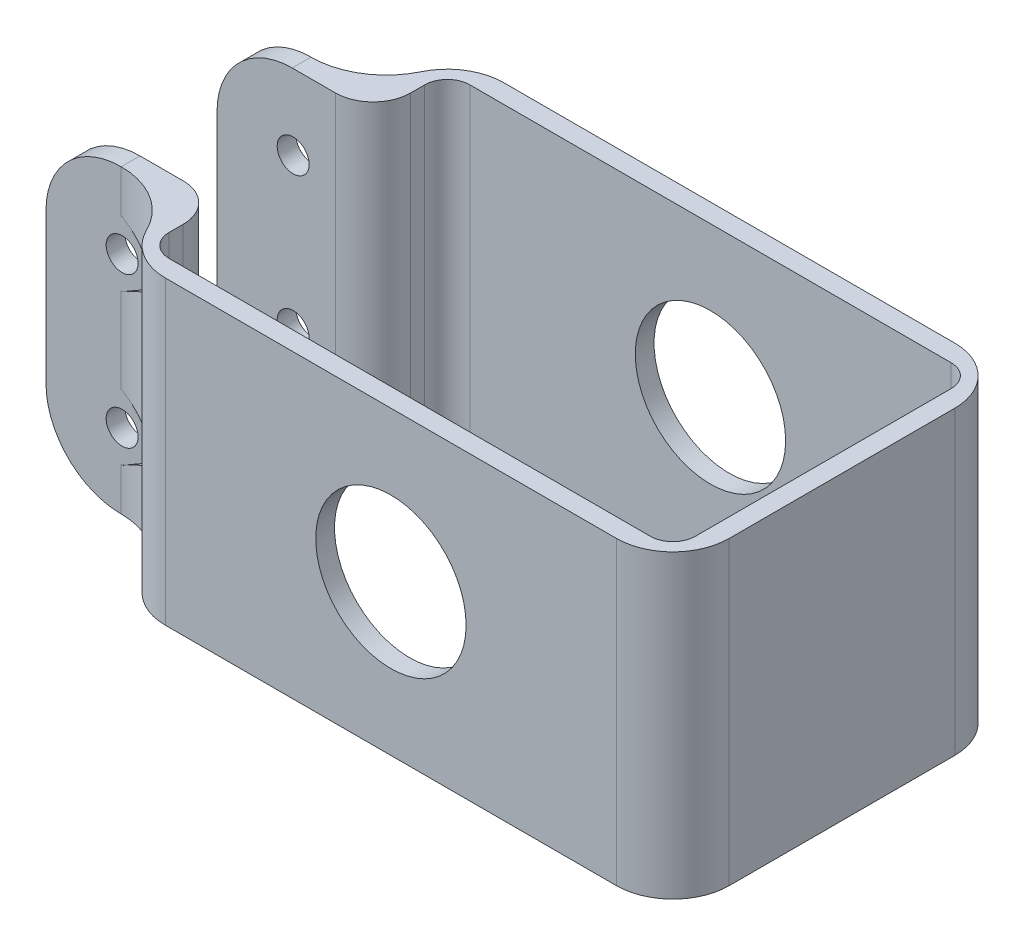
SolidWorks part; units mm, degrees
ref_plane "Front Plane" through (0, 0, 0) normal (0, 0, 1) x (1, 0, 0)
ref_plane "Top Plane" through (0, 0, 0) normal (0, 1, 0) x (1, 0, 0)
ref_plane "Right Plane" through (0, 0, 0) normal (1, 0, 0) x (0, 0, -1)
sketch "Sketch1" plane through (0, 0, 0) normal (0, 1, 0) x (1, 0, 0)
  line L0 (35, -23) -> (-35, -23) construction
  line L1 (35, -8) -> (35, -38) construction
  line L2 (-35, -38) -> (-35, -8) construction
  line L3 (-35, -23) -> (-53.25, -23) construction
  line L5 (-35, -33.125) -> (-53.25, -33.125)
  line L6 (-35, -33.125) -> (-35, -12.875)
  line L7 (-35, -12.875) -> (-53.25, -12.875)
  line L8 (-53.25, -33.125) -> (-53.25, -12.875)
  line L9 (-35, -33.125) -> (-53.25, -12.875) construction
  line L10 (-35, -12.875) -> (-53.25, -33.125) construction
  line L11 (-55.75, -10.375) -> (-35, -10.375)
  line L12 (-55.75, -10.375) -> (-55.75, -35.625)
  line L13 (-55.75, -35.625) -> (-35, -35.625)
  line L14 (-35, -10.375) -> (-35, -35.625)
  line L34 (-35, -10.375) -> (-35, -6)
  line L35 (-32, -3) -> (32, -3)
  line L36 (35, -6) -> (35, -40)
  line L37 (32, -43) -> (-32, -43)
  line L38 (30, -0.5) -> (-30, -0.5)
  line L39 (37.5, -38) -> (37.5, -8)
  line L40 (-30, -45.5) -> (30, -45.5)
  line L41 (-37.5, -8) -> (-37.5, -38)
  line L42 (30, -0.5) -> (-30, -0.5)
  line L43 (37.5, -38) -> (37.5, -8)
  line L44 (-30, -45.5) -> (30, -45.5)
  line L45 (-37.5, -8) -> (-37.5, -38)
  line L46 (-35, -40) -> (-35, -3)
  line L47 (-30, -3) -> (30, -3) construction
  line L48 (30, -43) -> (-30, -43) construction
  line L49 (-53.25, -12.875) -> (-55.75, -12.875)
  line L50 (-53.25, -33.125) -> (-55.75, -33.125)
  arc A22 (-35, -40) -> (-32, -43) centre (-32, -40) ccw
  arc A23 (32, -43) -> (35, -40) centre (32, -40) ccw
  arc A24 (35, -6) -> (32, -3) centre (32, -6) ccw
  arc A25 (-35, -6) -> (-32, -3) centre (-32, -6) cw
  arc A26 (37.5, -8) -> (30, -0.5) centre (30, -8) ccw
  arc A27 (30, -45.5) -> (37.5, -38) centre (30, -38) ccw
  arc A28 (-37.5, -38) -> (-30, -45.5) centre (-30, -38) ccw
  arc A29 (-30, -0.5) -> (-37.5, -8) centre (-30, -8) ccw
  arc A30 (37.5, -8) -> (30, -0.5) centre (30, -8) ccw
  arc A31 (30, -45.5) -> (37.5, -38) centre (30, -38) ccw
  arc A32 (-37.5, -38) -> (-30, -45.5) centre (-30, -38) ccw
  arc A33 (-30, -0.5) -> (-37.5, -8) centre (-30, -8) ccw
  point P6 (-44.125, -23)
  dimension "D7" = 3
  dimension "D1" = 20.25
  dimension "D2" = 18.25
  dimension "D3" = 2.5
  dimension "D4" = 2.5
  dimension "D5" = 2.5
  dimension "D6" = 2.5
extrude "Boss-Extrude1" add sketch "Sketch1" along normal blind 20 and the other way blind 20 contours L5 L50 L12 L13 L45 | L5 L45 L13 L14 | L42 A33 L45 L11 L34 A25 L35 A24 L36 A23 L37 A22 L46 L13 A32 L44 A31 L43 A30 | L11 L45 L7 L14 | L49 L7 L45 L11 L12 region at (-36.25, 0, 34.375) region at (-46.625, 0, 34.375) region at (-36.25, 0, 11.625) region at (-35.8746, 0, 37.8125) region at (-46.625, 0, 11.625)
fillet "Fillet1" radius 10 2 edges at (-37.5, 0, 10.375) (-37.5, 0, 35.625)
sketch "Sketch2" plane through (0, 0, 0) normal (0, 0, 1) x (1, 0, 0)
  line L0 (-45.625, 20) -> (-45.625, -20) construction
  line L1 (-55.75, 20) -> (-45.7515, 20) construction
  line L2 (-55.75, -20) -> (-45.7515, -20) construction
  line L3 (-55.75, -20) -> (-55.75, 20) construction
  circle A0 centre (-45.625, 10) radius 2.125
  circle A1 centre (-45.625, -10) radius 2.125
  circle A2 centre (-45.625, 10) radius 4.25
  circle A3 centre (-45.625, -10) radius 4.25
  dimension "D1" = 4.25
  dimension "D5" = 8.5
  dimension "D2" = 10.125
  dimension "D3" = 10
  dimension "D4" = 10
extrude "Cut-Extrude1" cut sketch "Sketch2" against normal through all both and the other way through all contours L0 A1 | A1 L0 | A0 L0 | L0 A0 region at (-44.7231, 10, 0) region at (-46.5269, 10, 0) region at (-44.7231, -10, 0) region at (-46.5269, -10, 0)
extrude "Cut-Extrude2" cut sketch "Sketch2<4>" along normal up to surface (10.375 mm away) and the other way through all contours A2 L0 A0 | A3 L0 A1 region at (-42.687, 12.938, 0) region at (-42.687, -7.062, 0) up to face at (-48.7507, 0, 10.375)
sketch "Sketch2<4>" plane through (0, 0, 0) normal (0, 0, 1) x (1, 0, 0) same geometry as "Sketch2"
ref_plane "Plane1" through (0, 0, 23) normal (0, 0, -1) x (-1, 0, 0)
fillet "Fillet2" radius 10 4 edges at (-55.75, -20, 11.625) (-55.75, -20, 34.375) (-55.75, 20, 11.625) (-55.75, 20, 34.375)
fillet "Fillet3" radius 5 2 edges at (-35, 0, 12.875) (-35, 0, 33.125)
sketch "Sketch3" plane through (0, 0, 35.625) normal (0, 0, 1) x (1, 0, 0)
  line L1 (-45.625, 14.3301) -> (-49.375, 12.1651)
  line L2 (-49.375, 12.1651) -> (-49.375, 7.8349)
  line L3 (-49.375, 7.8349) -> (-45.625, 5.6699)
  line L4 (-45.625, 5.6699) -> (-41.875, 7.8349)
  line L5 (-41.875, 7.8349) -> (-41.875, 12.1651)
  line L6 (-41.875, 12.1651) -> (-45.625, 14.3301)
  line L7 (-45.625, -5.6699) -> (-49.375, -7.8349)
  line L8 (-49.375, -7.8349) -> (-49.375, -12.1651)
  line L9 (-49.375, -12.1651) -> (-45.625, -14.3301)
  line L10 (-45.625, -14.3301) -> (-41.875, -12.1651)
  line L11 (-41.875, -12.1651) -> (-41.875, -7.8349)
  line L12 (-41.875, -7.8349) -> (-45.625, -5.6699)
  circle A0 centre (-45.625, 10) radius 3.75 construction
  circle A1 centre (-45.625, -10) radius 3.75 construction
  dimension "D1" = 7.5
extrude "Cut-Extrude3" cut sketch "Sketch3" along normal blind 20
sketch "Sketch4" plane through (0, 0, 45.5) normal (0, 0, 1) x (1, 0, 0)
  circle A0 centre (0, 0) radius 10
  dimension "D1" = 20
extrude "Cut-Extrude4" cut sketch "Sketch4" against normal through all both and the other way through all
